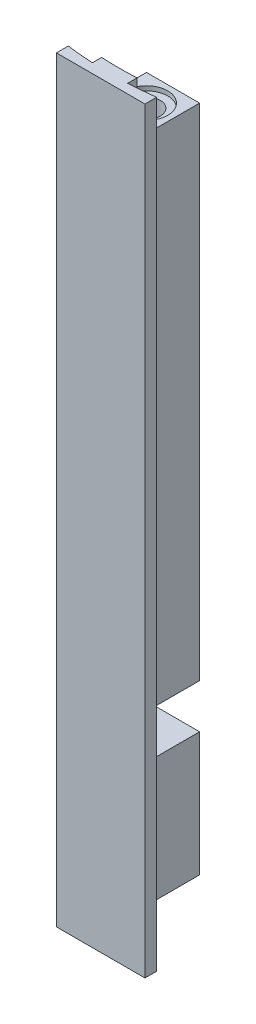
SolidWorks part; units mm, degrees
ref_plane "Front Plane" through (0, 0, 0) normal (0, 0, 1) x (1, 0, 0)
ref_plane "Top Plane" through (0, 0, 0) normal (0, 1, 0) x (1, 0, 0)
ref_plane "Right Plane" through (0, 0, 0) normal (1, 0, 0) x (0, 0, -1)
ref_plane "Plane7" through (0, -5, 0) normal (0, -1, 0) x (-1, 0, 0)
sketch "Sketch1" plane through (0, 0, 0) normal (0, 1, 0) x (1, 0, 0)
  circle A0 centre (0, 0) radius 37.5 construction
  dimension "D1" = 75
sketch "Sketch3" plane through (0, -5, 0) normal (0, -1, 0) x (1, 0, 0)
  line L0 (-3, 37.3798) -> (-3, 31.3798)
  line L1 (-3, 31.3798) -> (3, 31.3798)
  line L2 (3, 31.3798) -> (3, 37.3798)
  line L9 (0, 40.3758) -> (0, -39.6162) construction
  line L10 (0, -41.25) -> (0, 41.25) construction
  arc A0 (3, 37.3798) -> (-3, 37.3798) centre (0, 0) ccw
  circle A4 centre (0, 0) radius 37.5 construction
  dimension "D2" = 6
  dimension "D3" = 6
extrude "Boss-Extrude2" add sketch "Sketch3" along normal blind 75.5
sketch "Sketch5" plane through (0, 0, 0) normal (0, 1, 0) x (1, 0, 0)
  line L0 (-5, -38.2106) -> (-5, -39.2364)
  line L1 (5, -38.2315) -> (5, -39.2364)
  line L2 (2, -38.5052) -> (2, -37.4466)
  line L3 (-2, -38.4844) -> (-2, -37.4466)
  line L12 (0, 40.7328) -> (0, -41.0085) construction
  line L13 (0, -3.3661) -> (0, 3.3661) construction
  line L14 (0, -39.5537) -> (-5, -39.5537)
  line L15 (-5, -39.5537) -> (-5, -39.2364)
  line L16 (0, -39.5537) -> (5, -39.5537)
  line L17 (5, -39.5537) -> (5, -39.2364)
  arc A1 (-2, -37.4466) -> (2, -37.4466) centre (0, 0) ccw
  arc A2 (5, -38.2315) -> (2, -38.5052) centre (0, 0) cw
  arc A3 (-5, -38.2106) -> (-2, -38.4844) centre (0, 0) ccw
  circle A13 centre (0, 0) radius 37.5 construction
  dimension "D1" = 4
  dimension "D2" = 10
  dimension "D4" = 1.0049
extrude "Boss-Extrude3" add sketch "Sketch5" against normal blind 85.5
sketch "Sketch7" plane through (0, 0, 0) normal (1, 0, 0) x (0, 0, -1)
  line L0 (0, 3.3) -> (0, -3.3) construction
  line L1 (0, -61.5) -> (-37.5, -61.5)
  line L2 (0, -61.5) -> (0, -66.5)
  line L3 (0, -66.5) -> (-37.5, -66.5)
  line L4 (-37.5, -61.5) -> (-37.5, -66.5)
  line L6 (-31.3798, -80.5) -> (-37.3798, -80.5) construction
  line L7 (0, -27.0167) -> (0, -72.0117) construction
  dimension "D1" = 37.5
  dimension "D2" = 5
  dimension "D3" = 14
revolve "Cut-Revolve1" cut sketch "Sketch7" angle 360 about L7
ref_plane "Plane5" through (0, -80.5, 0) normal (0, -1, 0) x (-1, 0, 0)
sketch "Sketch9" plane through (0, -80.5, 0) normal (0, -1, 0) x (-1, 0, 0)
  line L0 (0, -31.1751) -> (0, -37.6667) construction
  line L1 (0, 3.3661) -> (0, -3.3661) construction
  line L2 (-3.1738, -34.4209) -> (3.1592, -34.4209) construction
  circle A0 centre (0, -34.4209) radius 1.55
  dimension "D2" = 3.1
extrude "Cut-Extrude4" cut sketch "Sketch9" against normal blind 4.3
sketch "Sketch10" plane through (0, -80.5, 0) normal (0, -1, 0) x (-1, 0, 0)
  line L0 (0, -31.1751) -> (0, -37.6667) construction
  line L2 (-3.1738, -34.4209) -> (3.1592, -34.4209) construction
  circle A0 centre (0, -34.4209) radius 2.4
  dimension "D2" = 4.8
extrude "Cut-Extrude5" cut sketch "Sketch10" against normal blind 0.5
sketch "Sketch12" plane through (0, -5, 0) normal (0, -1, 0) x (-1, 0, 0)
  circle A0 centre (0, 0) radius 37.5 construction
sketch "Sketch13" plane through (0, -5, 0) normal (0, -1, 0) x (-1, 0, 0)
  line L0 (0, -31.134) -> (0, -37.6256) construction
  line L1 (-2.6479, -34.3798) -> (2.8747, -34.3798) construction
  line L2 (3, -37.3798) -> (3, -31.3798) construction
  line L3 (-3, -31.3798) -> (-3, -37.3798) construction
  circle A0 centre (0, -34.3798) radius 2.4
sketch "Sketch14" plane through (0, -5, 0) normal (0, -1, 0) x (-1, 0, 0)
  line L0 (0, -31.134) -> (0, -37.6256) construction
  line L2 (-3.1738, -34.3798) -> (3.1592, -34.3798) construction
  line L3 (3, -37.3798) -> (3, -31.3798) construction
  line L4 (-3, -31.3798) -> (-3, -37.3798) construction
  circle A0 centre (0, -34.3798) radius 1.55
  dimension "D2" = 3.1
extrude "Cut-Extrude6" cut sketch "Sketch13" along normal blind 0.5
extrude "Cut-Extrude7" cut sketch "Sketch14" along normal blind 4.3
